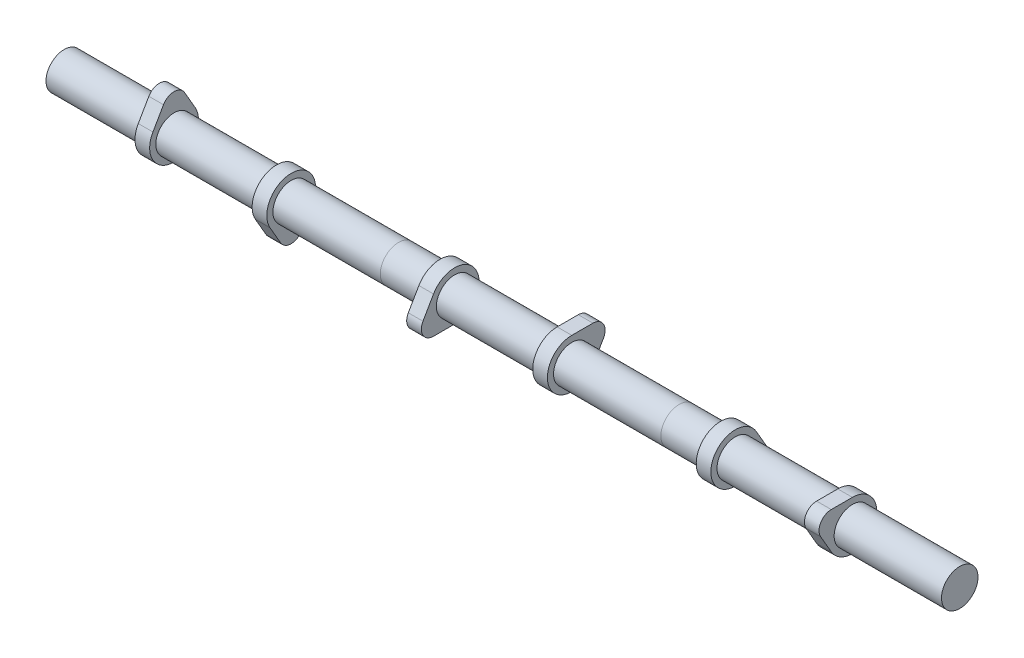
SolidWorks part; units mm, degrees
ref_plane "Front Plane" through (0, 0, 0) normal (0, 0, 1) x (1, 0, 0)
ref_plane "Top Plane" through (0, 0, 0) normal (0, 1, 0) x (1, 0, 0)
ref_plane "Right Plane" through (0, 0, 0) normal (1, 0, 0) x (0, 0, -1)
sketch "Sketch2" plane through (0, 0, 0) normal (1, 0, 0) x (0, 0, -1)
  line L0 (-5.4993, 15.875) -> (-10.9985, 6.35)
  line L1 (5.4993, 15.875) -> (10.9985, 6.35)
  arc A0 (-10.9985, 6.35) -> (10.9985, 6.35) centre (0, 0) ccw
  arc A3 (5.4993, 15.875) -> (-5.4993, 15.875) centre (0, 12.7) ccw
  dimension "D1" = 25.4
extrude "Boss-Extrude1" add sketch "Sketch2" along normal mid plane 7.62
ref_axis "Axis1" through (133.8375, 0, 0) along (-1, 0, 0)
move or copy body "Body-Move/Copy1" bodies to move or copy 101 copy yes number of copies 1 translate (60.96, 0, 0)
move or copy body "Body-Move/Copy2" bodies to move or copy 102 copy no rotation origin (0, 0, 0) rotation axis (1, 0, 0) rotation angle 180
sketch "Sketch3" plane through (0, 0, 0) normal (1, 0, 0) x (0, 0, -1)
  circle A0 centre (0, 0) radius 9.5
  dimension "D1" = 19
extrude "Boss-Extrude2" add sketch "Sketch3" along normal blind 146.05 from offset 25.4 offset against normal yes
pattern_linear "LPattern1" count 3 spacing 146.05 along (1, 0, 0) of bodies 104
move or copy body "Body-Move/Copy3" bodies to move or copy 105 copy no rotation origin (0, 0, 0) rotation axis (1, 0, 0) rotation angle 120
move or copy body "Body-Move/Copy4" bodies to move or copy 106 copy no rotation origin (0, 0, 0) rotation axis (-1, 0, 0) rotation angle 120
sketch "Sketch4" plane through (-25.4, 0, 0) normal (-1, 0, 0) x (0, 0, 1)
  circle A1 centre (0, 0) radius 9.5
  circle A2 centre (0, 0) radius 9.5
  dimension "D1" = 0
extrude "Boss-Extrude3" add sketch "Sketch4" along normal blind 27.94
